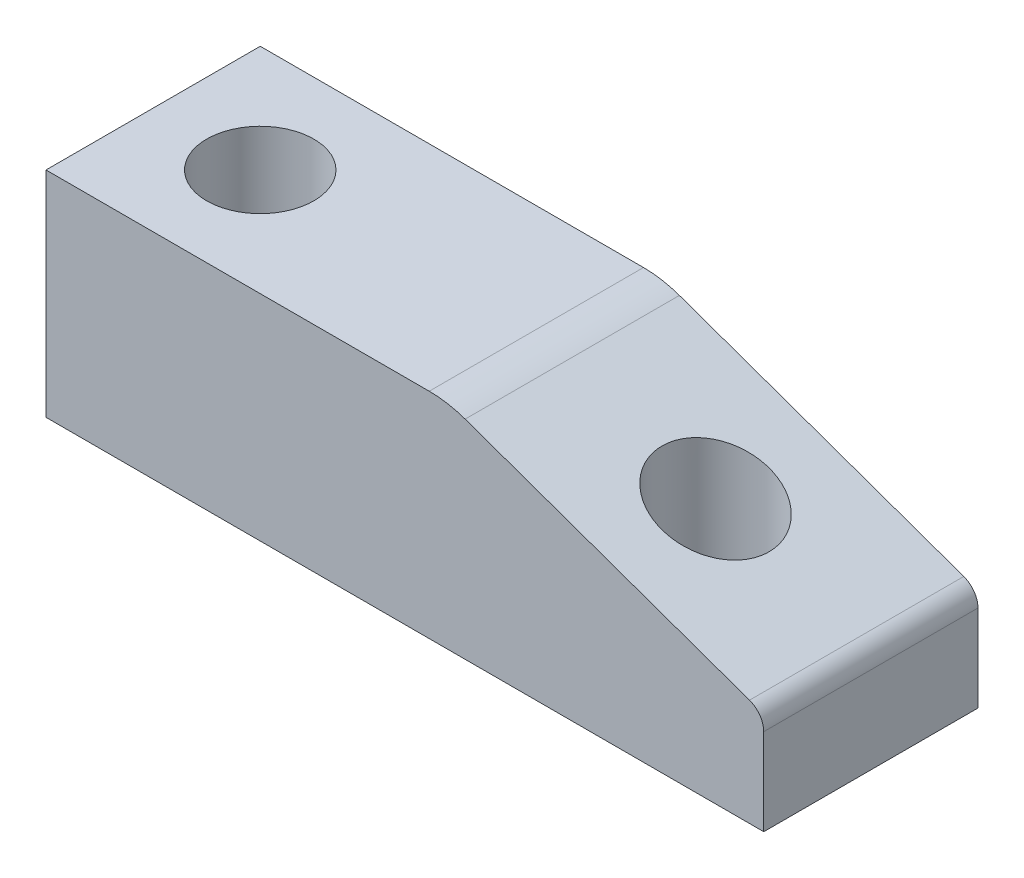
SolidWorks part; units mm, degrees
ref_plane "Front Plane" through (0, 0, 0) normal (0, 0, 1) x (1, 0, 0)
ref_plane "Top Plane" through (0, 0, 0) normal (0, 1, 0) x (1, 0, 0)
ref_plane "Right Plane" through (0, 0, 0) normal (1, 0, 0) x (0, 0, -1)
sketch "Sketch1" plane through (0, 0, 0) normal (0, 1, 0) x (1, 0, 0)
  line L0 (20, 63.9006) -> (20, -23.9006) construction
  line L1 (0, 0) -> (134, 0)
  line L2 (0, 0) -> (0, 40)
  line L3 (0, 40) -> (134, 40)
  line L4 (134, 0) -> (134, 40)
  line L5 (105, -23.9006) -> (105, 63.9006) construction
  line L6 (-13.5506, 20) -> (142.4949, 20) construction
  line L7 (75, 40) -> (75, 0)
  circle A0 centre (20, 20) radius 10
  circle A1 centre (20, 20) radius 6
  circle A2 centre (105, 20) radius 10
  circle A4 centre (105, 20) radius 6
  dimension "D6" = 20
  dimension "D7" = 12
  dimension "D8" = 12
  dimension "D9" = 20
  dimension "D1" = 134
  dimension "D2" = 40
  dimension "D3" = 20
  dimension "D4" = 85
  dimension "D5" = 20
  dimension "D10" = 75
extrude "Boss-Extrude1" add sketch "Sketch1" along normal blind 40 contours L7 L3 L2 L1 A0 region at (39.547, 0, -20)
extrude "Boss-Extrude2" add sketch "Sketch1<4>" along normal blind 40 contours L3 L7 L1 L4 A2 region at (75.7128, 0, -20)
sketch "Sketch1<4>" plane through (0, 0, 0) normal (0, 1, 0) x (1, 0, 0) same geometry as "Sketch1"
sketch "Sketch2" plane through (0, 40, 0) normal (0, 1, 0) x (1, 0, 0)
  line L0 (75, 40) -> (75, 0)
  line L1 (0, 40) -> (134, 40) construction
  line L2 (0, 0) -> (134, 0) construction
  line L3 (0, 0) -> (0, 40) construction
  dimension "D1" = 75
sketch "Sketch3" plane through (0, 0, 0) normal (0, 0, 1) x (1, 0, 0)
  line L1 (134, 40) -> (134, 0) construction
  line L2 (134, 19) -> (75, 40)
  line L3 (0, 40) -> (134, 40) construction
  dimension "D2" = 75
sketch "Sketch4" plane through (134, 0, 0) normal (1, 0, 0) x (0, 0, -1)
  line L0 (0, 19) -> (40, 19)
  line L1 (0, 19) -> (0, 40) construction
  line L2 (0, 40) -> (0, 0) construction
  line L3 (40, 40) -> (40, 0) construction
sketch "Sketch5" plane through (0, 0, -40) normal (0, 0, -1) x (-1, 0, 0)
  line L0 (-134, 19) -> (-75, 40)
extrude "Cut-Extrude2" cut sketch "Sketch5" against normal blind 40 and the other way through all
fillet "Fillet2" radius 20 1 edges at (75, 40, -20)
fillet "Fillet3" radius 4 1 edges at (134, 19, -20)
extrude "Boss-Extrude3" add sketch "Sketch1<5>" along normal blind 10 contours A0 A1 | A2 A4 region at (10.2828, 0, -20) region at (95.2828, 0, -20)
sketch "Sketch1<5>" plane through (0, 0, 0) normal (0, 1, 0) x (1, 0, 0) same geometry as "Sketch1"
